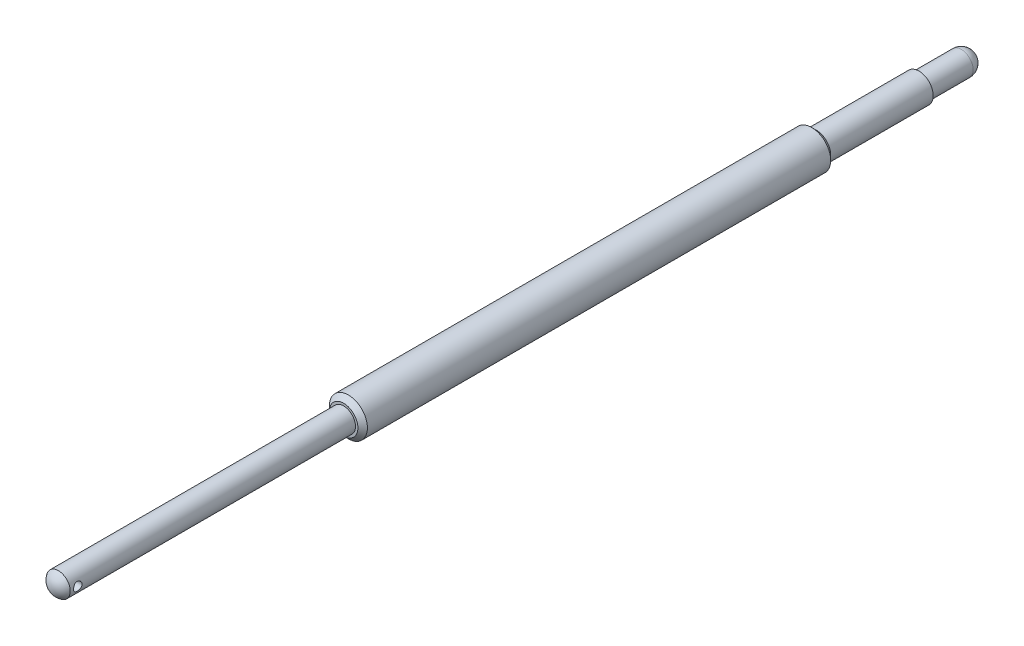
SolidWorks part; units mm, degrees
ref_plane "Front Plane" through (0, 0, 0) normal (0, 0, 1) x (1, 0, 0)
ref_plane "Top Plane" through (0, 0, 0) normal (0, 1, 0) x (1, 0, 0)
ref_plane "Right Plane" through (0, 0, 0) normal (1, 0, 0) x (0, 0, -1)
sketch "Sketch1" plane through (0, 0, 0) normal (0, 0, 1) x (1, 0, 0)
  circle A0 centre (0, 0) radius 1.25 construction
  circle A1 centre (0, 0) radius 1.25
sketch "Sketch2" plane through (0, 0, 0) normal (1, 0, 0) x (0, 0, -1)
  line L0 (-29.2339, 0) -> (65.5, 0)
  line L2 (64.95, -1.25) -> (60.5, -1.25)
  line L3 (60.5, -1.25) -> (60.5, -1.5)
  line L4 (60.5, -1.5) -> (49.7192, -1.5)
  line L5 (49.7192, -1.5) -> (49.7192, -2)
  line L6 (49.7192, -2) -> (0, -2)
  line L7 (0, -2) -> (0, -1.25)
  line L8 (0, -1.25) -> (-5, -1.25)
  line L9 (-5, 23.0761) -> (-5, -73.5) construction
  line L10 (65.5, 0) -> (66.2, 0)
  line L11 (49.7192, -1.5) -> (0, -1.5) construction
  line L12 (-29.2339, 0) -> (-30.7, 0)
  line L13 (-30, -1.25) -> (-5, -1.25)
  arc A1 (64.95, -1.25) -> (66.2, 0) centre (64.95, 0) ccw
  arc A2 (-30.7, 0) -> (-30, -1.25) centre (-29.2339, 0) ccw
  dimension "D1" = 25
  dimension "D2" = 0.7
  dimension "D3" = 0.7
revolve "Revolve1" add sketch "Sketch2" angle 360 about L0
chamfer "Chamfer1" distance 0.5 angle 45 2 edges at (2, 0, 0) (2, 0, -49.7192)
sketch "Sketch3" plane through (0, 0, 0) normal (1, 0, 0) x (0, 0, -1)
  line L0 (-30, 1.25) -> (-30, -1.25) construction
  circle A0 centre (-29.2, 0) radius 0.45
  dimension "D1" = 0.9
  dimension "D2" = 0.8
extrude "Cut-Extrude1" cut sketch "Sketch3" against normal through all both and the other way through all
